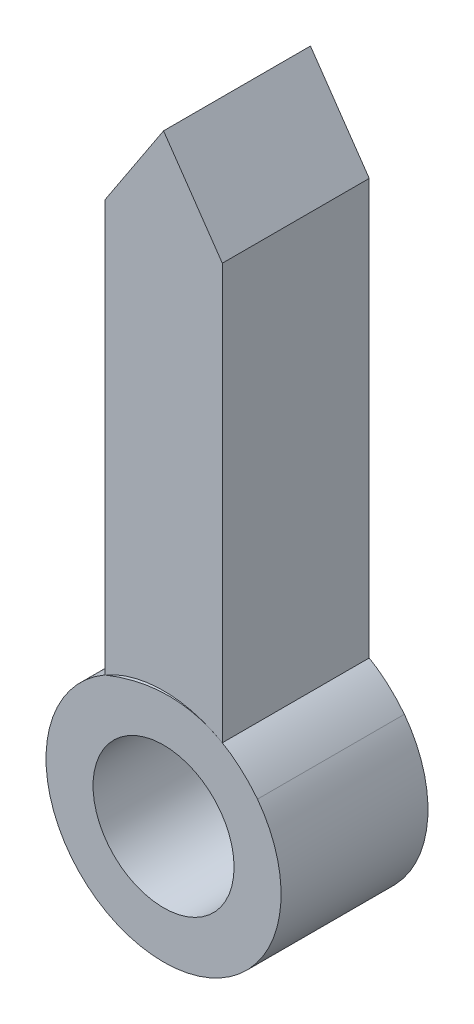
SolidWorks part; units mm, degrees
ref_plane "Front Plane" through (0, 0, 0) normal (0, 0, 1) x (1, 0, 0)
ref_plane "Top Plane" through (0, 0, 0) normal (0, 1, 0) x (1, 0, 0)
ref_plane "Right Plane" through (0, 0, 0) normal (1, 0, 0) x (0, 0, -1)
sketch "Sketch1" plane through (0, 0, 0) normal (0, 0, 1) x (1, 0, 0)
  line L0 (-1.27, 2.1997) -> (-1.27, 11.0897)
  line L1 (1.27, 2.1997) -> (1.27, 11.0897)
  line L2 (0, 9.652) -> (0, -11.7615) construction
  line L3 (-1.27, 11.0897) -> (0, 13.0192)
  line L4 (0, 13.0192) -> (1.27, 11.176)
  line L5 (1.27, 11.2036) -> (1.27, 11.0897)
  circle A0 centre (0, 0) radius 1.524
  circle A1 centre (0, 0) radius 2.54
  spline S0 degree 2 poles (-1.27, 2.1997) (0.8273, 3.0418) (2.0304, 1.5261) knots 0 0 0 1 1 1
  dimension "D1" = 3.048
  dimension "D2" = 5.08
  dimension "D3" = 2.54
  dimension "D4" = 8.89
extrude "Boss-Extrude1" add sketch "Sketch1" along normal blind 3.175 contours A1 L2 A0 | L2 A1 A0 region at (-0.6339, 2.3478, 0) region at (0.0564, -2.032, 0)
extrude "Boss-Extrude2" add sketch "Sketch1<4>" along normal blind 3.175 separate body contours A1 L1 L5 L4 L3 L0 region at (0.0019, 7.2678, 0)
sketch "Sketch1<4>" plane through (0, 0, 0) normal (0, 0, 1) x (1, 0, 0) same geometry as "Sketch1"
